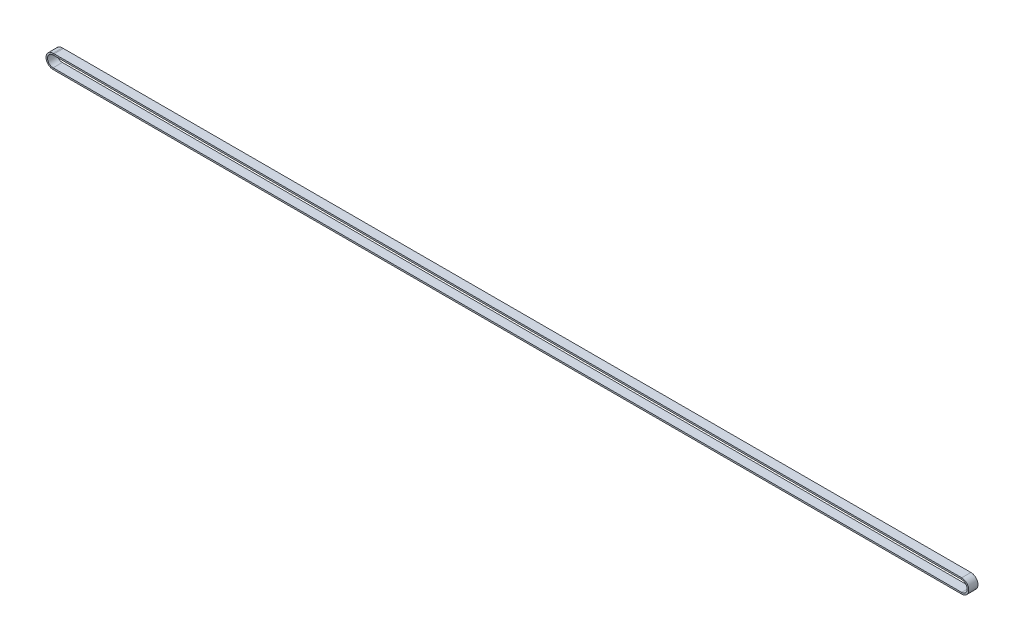
SolidWorks part; units mm, degrees
ref_plane "Front Plane" through (0, 0, 0) normal (0, 0, 1) x (1, 0, 0)
ref_plane "Top Plane" through (0, 0, 0) normal (0, 1, 0) x (1, 0, 0)
ref_plane "Right Plane" through (0, 0, 0) normal (1, 0, 0) x (0, 0, -1)
sketch "Sketch2" plane through (0, 0, -121.9834) normal (0, 0, 1) x (1, 0, 0)
  line L0 (0, 0) -> (1, 0) construction
  line L1 (0, 0) -> (0, 1) construction
  line L2 (-1, 148.3734) -> (883.5206, 148.3734)
  line L3 (883.5206, 134.5734) -> (-1, 134.5734)
  arc A0 (-1, 134.5734) -> (-1, 148.3734) centre (-1, 141.4734) cw
  arc A1 (883.5206, 148.3734) -> (883.5206, 134.5734) centre (883.5206, 141.4734) cw
sketch "Sketch3" plane through (0, 0, 0) normal (1, 0, 0) x (0, 0, -1)
  line L1 (121.9834, 146.8734) -> (112.9834, 146.8734)
  line L2 (121.9834, 146.8734) -> (121.9834, 148.3734)
  line L3 (121.9834, 148.3734) -> (112.9834, 148.3734)
  line L4 (112.9834, 146.8734) -> (112.9834, 148.3734)
  dimension "D1" = 9
  dimension "D2" = 1.5
sweep "Sweep1" add profiles "Sketch3" path "Sketch2"
